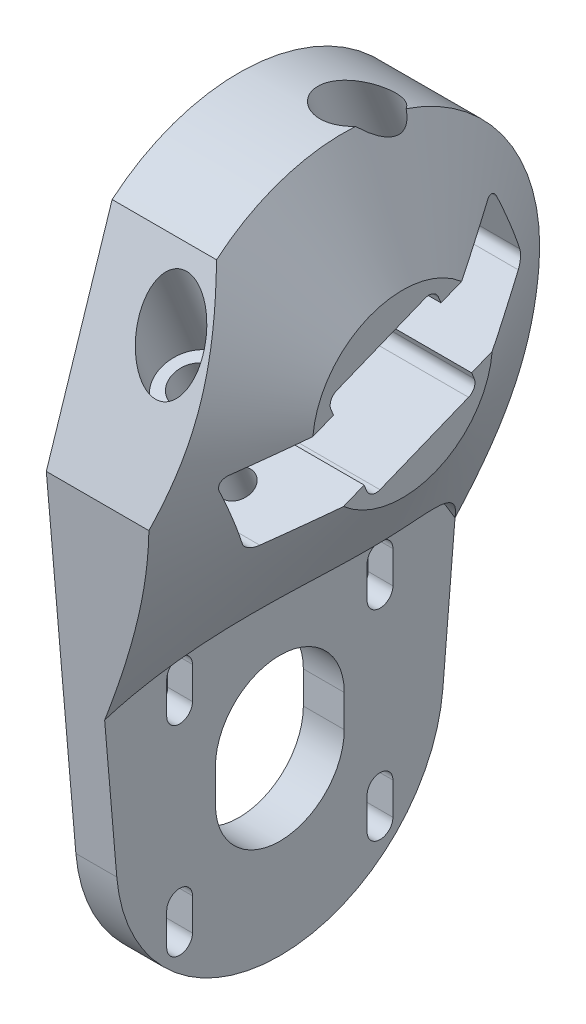
SolidWorks part; units mm, degrees
ref_plane "Front Plane" through (0, 0, 0) normal (0, 0, 1) x (1, 0, 0)
ref_plane "Top Plane" through (0, 0, 0) normal (0, 1, 0) x (1, 0, 0)
ref_plane "Right Plane" through (0, 0, 0) normal (1, 0, 0) x (0, 0, -1)
sketch "Sketch1" plane through (0, 0, 0) normal (1, 0, 0) x (0, 0, -1)
  line L0 (4.9732, 11.7161) -> (-11.7161, 4.9732)
  line L1 (4.9732, 11.7161) -> (11.7161, -4.9732)
  line L2 (-11.7161, 4.9732) -> (-4.9732, -11.7161)
  line L3 (11.7161, -4.9732) -> (-4.9732, -11.7161)
  line L4 (4.9732, 11.7161) -> (-4.9732, -11.7161) construction
  line L5 (-11.7161, 4.9732) -> (11.7161, -4.9732) construction
  line L6 (0, 0) -> (0, -57.15) construction
  line L7 (-30.3693, -2.5958) -> (-25.3077, -61.8132)
  line L8 (25.3077, -61.8132) -> (30.3693, -2.5958)
  line L9 (0, -57.15) -> (0, -103.9417) construction
  arc A0 (30.3693, -2.5958) -> (-30.3693, -2.5958) centre (0, 0) ccw
  arc A1 (-25.3077, -61.8132) -> (25.3077, -61.8132) centre (0, -59.65) ccw
  dimension "D1" = 2.5
  dimension "D2" = 30.48
  dimension "D6" = 57.15
  dimension "D7" = 25.4
  dimension "D8" = 0
  dimension "D3" = 18
  dimension "D4" = 18
  dimension "D5" = 22
extrude "Boss-Extrude1" add sketch "Sketch1" along normal blind 6.35 contours L7 A0 L1 L3 L2 L0 region at (0, -27.1671, 0)
sketch "Sketch19" plane through (6.35, 0, 0) normal (1, 0, 0) x (0, 0, -1)
  line L0 (0, -59.65) -> (0, -54.65)
  line L1 (0, -54.65) -> (15.5563, -39.0937) construction
  line L2 (15.5563, -44.0937) -> (15.5563, -39.0937) construction
  line L3 (13.5563, -44.0937) -> (13.5563, -39.0937)
  line L4 (17.5563, -44.0937) -> (17.5563, -39.0937)
  line L5 (-10, -59.65) -> (-10, -54.65)
  line L6 (10, -59.65) -> (10, -54.65)
  line L7 (0, -57.15) -> (7.4061, -57.15) construction
  line L8 (15.5563, -44.0937) -> (0, -59.65) construction
  line L9 (17.5563, -70.2063) -> (17.5563, -75.2063)
  line L10 (13.5563, -70.2063) -> (13.5563, -75.2063)
  line L11 (-17.5563, -44.0937) -> (-17.5563, -39.0937)
  line L12 (-13.5563, -44.0937) -> (-13.5563, -39.0937)
  line L13 (-13.5563, -70.2063) -> (-13.5563, -75.2063)
  line L14 (-17.5563, -70.2063) -> (-17.5563, -75.2063)
  line L15 (-15.5563, -44.0937) -> (0, -59.65) construction
  line L16 (0, -59.65) -> (-15.5563, -75.2063) construction
  line L17 (0, -59.65) -> (15.5563, -75.2063) construction
  arc A0 (-25.3077, -61.8132) -> (25.3077, -61.8132) centre (0, -59.65) ccw construction
  arc A1 (-25.3077, -61.8132) -> (25.3077, -61.8132) centre (0, -59.65) ccw
  arc A2 (-10, -59.65) -> (10, -59.65) centre (0, -59.65) ccw
  arc A3 (17.5563, -75.2063) -> (13.5563, -75.2063) centre (15.5563, -75.2063) cw
  arc A4 (13.5563, -70.2063) -> (17.5563, -70.2063) centre (15.5563, -70.2063) cw
  arc A6 (17.5563, -39.0937) -> (13.5563, -39.0937) centre (15.5563, -39.0937) ccw
  arc A7 (13.5563, -44.0937) -> (17.5563, -44.0937) centre (15.5563, -44.0937) ccw
  arc A8 (-17.5563, -39.0937) -> (-13.5563, -39.0937) centre (-15.5563, -39.0937) cw
  arc A9 (10, -54.65) -> (-10, -54.65) centre (0, -54.65) ccw
  arc A10 (-13.5563, -44.0937) -> (-17.5563, -44.0937) centre (-15.5563, -44.0937) cw
  arc A11 (-13.5563, -70.2063) -> (-17.5563, -70.2063) centre (-15.5563, -70.2063) ccw
  arc A13 (-17.5563, -75.2063) -> (-13.5563, -75.2063) centre (-15.5563, -75.2063) ccw
  point P8 (0, -57.15)
  dimension "D1" = 135
  dimension "D3" = 22
  dimension "D5" = 4
  dimension "D6" = 5
  dimension "D4" = 4
  dimension "D8" = 0
  dimension "D2" = 5
  dimension "D7" = 45
extrude "Cut-Extrude18" cut sketch "Sketch19" against normal blind 10 contours L6 A9 L5 A2 | A10 L12 A8 L11 | L14 A13 L13 A11 | A4 L10 A3 L9 | L4 A6 L3 A7 region at (6.35, -57.15, 9.6798) region at (6.35, -72.7063, -15.5563) region at (6.35, -41.5937, 15.5563) region at (6.35, -72.7063, 15.5563)
sketch "Sketch20" plane through (6.35, 0, 0) normal (1, 0, 0) x (0, 0, -1)
  circle A0 centre (0, 0) radius 57.15
  arc A1 (-25.3077, -61.8132) -> (25.3077, -61.8132) centre (0, -59.65) ccw construction
  point P3 (0, -85.05)
extrude "Boss-Extrude5" add sketch "Sketch20" along normal blind 19.05
sketch "Sketch21" plane through (0, 0, 0) normal (-1, 0, 0) x (0, 0, 1)
  line L0 (-24.6312, 3.1029) -> (-10.7234, -2.5162)
  line L1 (11.7161, 4.9732) -> (4.9732, -11.7161) construction
  line L2 (3.3715, 8.3447) -> (-3.3715, -8.3447) construction
  line L3 (-4.9732, 11.7161) -> (-11.7161, -4.9732) construction
  line L4 (-4.9732, 11.7161) -> (11.7161, 4.9732) construction
  line L5 (11.7161, 4.9732) -> (10.7234, 2.5162)
  line L6 (-11.7161, -4.9732) -> (4.9732, -11.7161) construction
  line L7 (-4.9732, 11.7161) -> (-5.9659, 9.2591)
  line L8 (-4.9732, 11.7161) -> (11.7161, 4.9732)
  line L9 (-22.2524, 8.9906) -> (-25.8466, 10.4427) construction
  line L10 (18.9617, -14.5097) -> (5.9659, -9.2591)
  line L11 (18.9617, -14.5097) -> (23.7193, -2.7345)
  line L12 (-24.6312, 3.1029) -> (-19.8737, 14.8782)
  line L13 (23.7193, -2.7345) -> (10.7234, 2.5162)
  line L16 (4.9732, -11.7161) -> (5.9659, -9.2591)
  line L17 (-11.7161, -4.9732) -> (-10.7234, -2.5162)
  line L18 (11.7161, 4.9732) -> (-4.9732, 11.7161)
  line L21 (-10.7234, -2.5162) -> (-11.7161, -4.9732)
  line L24 (-10.7234, -2.5162) -> (-24.6312, 3.1029)
  line L27 (-5.9659, 9.2591) -> (-4.9732, 11.7161)
  line L29 (-5.9659, 9.2591) -> (-19.8737, 14.8782)
  line L30 (5.9659, -9.2591) -> (4.9732, -11.7161)
  line L31 (10.7234, 2.5162) -> (11.7161, 4.9732)
  point P4 (-22.2524, 8.9906)
  line M13 (-11.7161, -4.9732) -> (-4.9732, 11.7161)
  line M14 (-4.9732, 11.7161) -> (11.7161, 4.9732)
  line M15 (11.7161, 4.9732) -> (4.9732, -11.7161)
  line M16 (4.9732, -11.7161) -> (-11.7161, -4.9732)
  dimension "D1" = 15
  dimension "D2" = 12.7
extrude "Cut-Extrude14" cut sketch "Sketch21" against normal through all contours L29 L12 L0 M13 | M13 M16 M15 M14 | L11 L13 L10 M15 region at (0, 6.181, -15.2985) region at (0, 0, 0) region at (0, -5.9968, 14.8426)
sketch "Sketch22" plane through (0, 5.8876, 2.3788) normal (0, -0.9272, -0.3746) x (-1, 0, 0)
  line L0 (-25.4, -9) -> (0, -9) construction
  line L2 (0, -29.1303) -> (0, 30.48) construction
  circle A0 centre (-12.5, -16.5) radius 3.175
  dimension "D2" = 12.5
  dimension "D3" = 6.35
  dimension "D1" = 7.5
extrude "Cut-Extrude15" cut sketch "Sketch22" against normal through all
ref_plane "Plane1" through (0, 10.5977, 4.2818) normal (0, -0.9272, -0.3746) x (-1, 0, 0)
sketch "Sketch24" plane through (0, 10.5977, 4.2818) normal (0, -0.9272, -0.3746) x (-1, 0, 0)
  circle A0 centre (-12.5, -16.5) radius 5
  dimension "D1" = 10
extrude "Cut-Extrude16" cut sketch "Sketch24" against normal through all
sketch "Sketch25" plane through (0, -5.8876, -2.3788) normal (0, 0.9272, 0.3746) x (1, 0, 0)
  circle A0 centre (12.5, -16.5) radius 3.175 construction
  circle A1 centre (12.5, -16.5) radius 3.175
  circle A2 centre (12.5, -16.5) radius 2.3813
  dimension "D1" = 0.7937
extrude "Cut-Extrude17" cut sketch "Sketch25" against normal blind 10 contours A2 region at (12.5, -12.0686, 12.9198)
ref_plane "Plane2" through (0, 0, 0) normal (0, 0.3746, -0.9272) x (-1, 0, 0)
mirror "Mirror1" about plane through (0, 0, 0) normal (0, 0.3746, -0.9272) of "Cut-Extrude17", "Cut-Extrude15", "Cut-Extrude16"
mirror "Mirror2" about plane through (0, 0, 0) normal (1, 0, 0) of bodies 124 126
delete or keep bodies "Body-Delete/Keep 1" type delete bodies bodies 127
chamfer "Chamfer2" distance 2.5 angle 45 8 edges at (0, -46.0937, 15.5563) (0, -41.5937, 13.5563) (0, -37.0937, 15.5563) (0, -41.5937, 17.5563) (0, -46.0937, -15.5563) (0, -41.5937, -17.5563) (0, -41.5937, -13.5563) (0, -37.0937, -15.5563)
sketch "Sketch26" plane through (0, 0, 0) normal (-1, 0, 0) x (0, 0, 1)
  line L0 (11.4538, -58.2291) -> (27.0119, -8.4408)
  line L1 (0, 0) -> (0, -54.65) construction
  circle A0 centre (0, -54.65) radius 12
  circle A1 centre (0, 0) radius 28.3
  dimension "D1" = 24
  dimension "D2" = 56.6
fillet "Fillet1" radius 1.5875 8 edges at (12.7, -4.9732, -11.7161) (12.7, 3.1029, -24.6312) (12.7, 11.7161, -4.9732) (12.7, 14.8782, -19.8737) (12.7, -2.7345, 23.7193) (12.7, 4.9732, 11.7161) (12.7, -11.7161, 4.9732) (12.7, -14.5097, 18.9617)
sketch "Sketch28" plane through (6.35, 0, 0) normal (1, 0, 0) x (0, 0, -1)
  arc A0 (-10, -54.65) -> (10, -54.65) centre (0, -54.65) ccw construction
  arc A1 (-10, -54.65) -> (10, -54.65) centre (0, -54.65) ccw
  circle A3 centre (0, -54.65) radius 31
  dimension "D1" = 62
extrude "Cut-Extrude19" cut sketch "Sketch28" along normal through all contours A3
sketch "Sketch29" plane through (25.4, 0, 0) normal (1, 0, 0) x (0, 0, -1)
  arc A1 (30.3693, -2.5958) -> (-30.3693, -2.5958) centre (0, 0) ccw construction
  arc A2 (30.3693, -2.5958) -> (-30.3693, -2.5958) centre (0, 0) ccw
  circle A3 centre (0, 0) radius 13.97
sketch "Sketch30" plane through (6.35, 0, 0) normal (1, 0, 0) x (0, 0, -1)
  circle A0 centre (0, 0) radius 48.173
sketch "Sketch31" plane through (0, 0, 0) normal (0, 1, 0) x (1, 0, 0)
  line L0 (25.4, -13.97) -> (25.4, 13.97) construction
  line L1 (25.4, -13.97) -> (25.4, 13.97)
  line L2 (6.35, -48.173) -> (6.35, 48.173) construction
  line L3 (6.35, -48.173) -> (6.35, 48.173)
  line L4 (25.4, -13.97) -> (6.35, -48.173)
  line L5 (6.35, -48.173) -> (6.35, -59.9521)
  line L6 (6.35, -59.9521) -> (25.4, -59.9521)
  line L7 (25.4, -59.9521) -> (25.4, -13.97)
  line L8 (25.4, 0) -> (0, 0) construction
revolve "Cut-Revolve1" cut sketch "Sketch31" angle 360 about L8 region at (17.7551, 0, 43.824)
sketch "Sketch32" plane through (6.35, 0, 0) normal (-1, 0, 0) x (0, 0, 1)
  line L0 (30.3693, -2.5958) -> (25.3077, -61.8132) construction
  line L1 (-25.3077, -61.8132) -> (-30.3693, -2.5958) construction
  line L2 (30.3693, -2.5958) -> (25.3077, -61.8132)
  line L3 (-25.3077, -61.8132) -> (-30.3693, -2.5958)
  arc A0 (30.3693, -2.5958) -> (-30.3693, -2.5958) centre (0, 0) ccw construction
  arc A1 (30.3693, -2.5958) -> (-30.3693, -2.5958) centre (0, 0) ccw
  circle A2 centre (0, 0) radius 48.173 construction
  circle A3 centre (0, 0) radius 48.173
  arc M2 (27.1923, -39.7645) -> (-27.1923, -39.7645) centre (0, 0) ccw
  line M3 (-27.1923, -39.7645) -> (-30.3693, -2.5958)
  arc M4 (-30.3693, -2.5958) -> (30.3693, -2.5958) centre (0, 0) cw
  line M5 (30.3693, -2.5958) -> (27.1923, -39.7645)
extrude "Cut-Extrude20" cut sketch "Sketch32" against normal through all contours M5 M2 M3 M4 region at (6.35, 31.7844, 0)
sketch "Sketch33" plane through (0, 0, 0) normal (-1, 0, 0) x (0, 0, 1)
  line L0 (30.3693, -2.5958) -> (25.3077, -61.8132) construction
  line L1 (30.3693, -2.5958) -> (25.3077, -61.8132)
  line L2 (29.8935, -8.1625) -> (19.6783, 23.2765)
  line L3 (22.2473, -2.1398) -> (10.7234, 2.5162) construction
  arc A0 (30.3693, -2.5958) -> (-30.3693, -2.5958) centre (0, 0) ccw construction
  arc A1 (30.3693, -2.5958) -> (-30.3693, -2.5958) centre (0, 0) ccw
  arc M35 (30.3693, -2.5958) -> (-30.3693, -2.5958) centre (0, 0) ccw
  dimension "D1" = 50
  dimension "D2" = 25.908
extrude "Cut-Extrude21" cut sketch "Sketch33" against normal through all contours L2 L1 M35 region at (0, 8.4647, 26.4169)
equation "\".75i\"=14.27"
